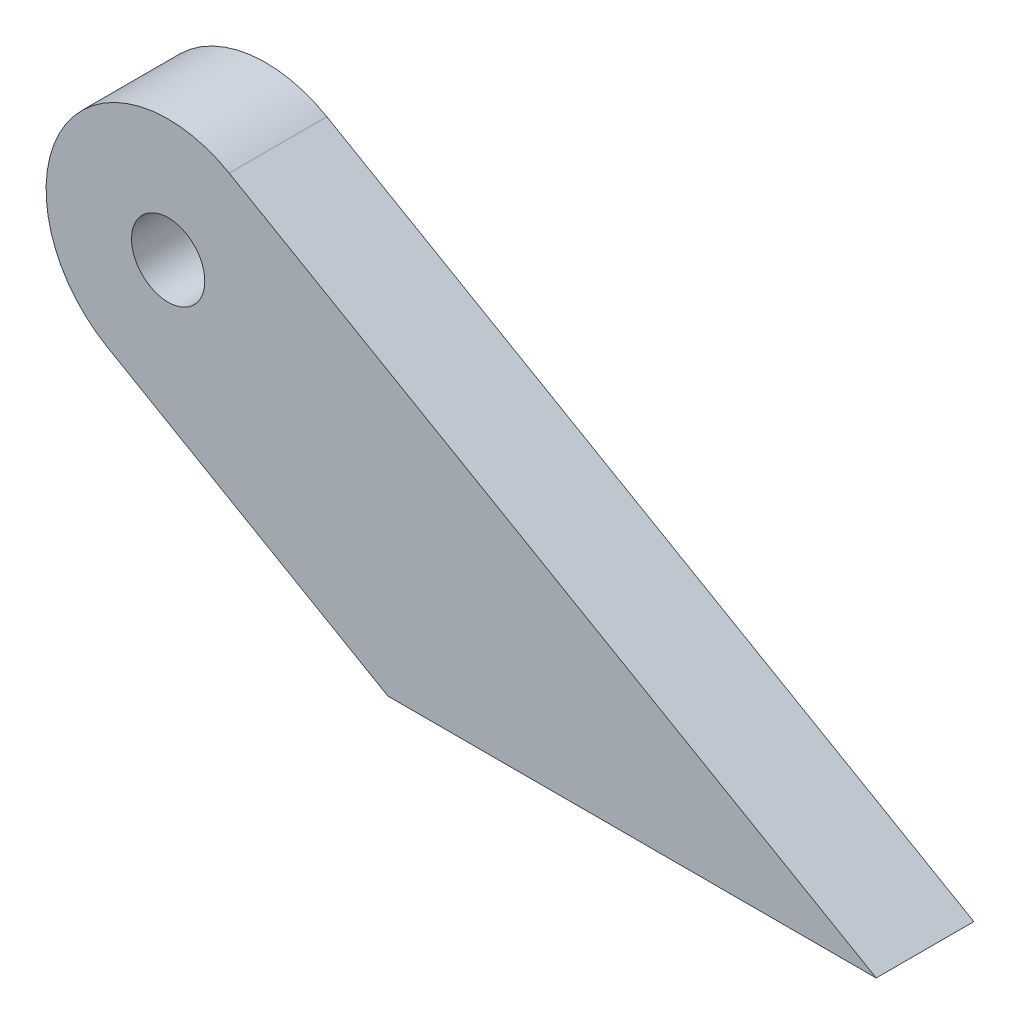
SolidWorks part; units mm, degrees
ref_plane "Front Plane" through (0, 0, 0) normal (0, 0, 1) x (1, 0, 0)
ref_plane "Top Plane" through (0, 0, 0) normal (0, 1, 0) x (1, 0, 0)
ref_plane "Right Plane" through (0, 0, 0) normal (1, 0, 0) x (0, 0, -1)
sketch "Sketch1" plane through (0, 0, 0) normal (0, 0, 1) x (1, 0, 0)
  line L0 (0, 0) -> (10, 0)
  line L1 (10, 0) -> (-3.25, 7.6499)
  line L2 (-4.5, 5.4848) -> (-4.5, 13.0096) construction
  line L3 (-5.75, 3.3198) -> (0, 0)
  arc A0 (-3.25, 7.6499) -> (-5.75, 3.3198) centre (-4.5, 5.4848) ccw
  circle A1 centre (-4.5, 5.4848) radius 0.75
  dimension "D2" = 1.5
  dimension "D4" = 4.5
  dimension "D1" = 10
  dimension "D3" = 5
extrude "Boss-Extrude1" add sketch "Sketch1" along normal blind 2
ref_point "Point1"
ref_axis "Axis1" through (-4.5, 14.6866, 2) along (0, -1, 0)
